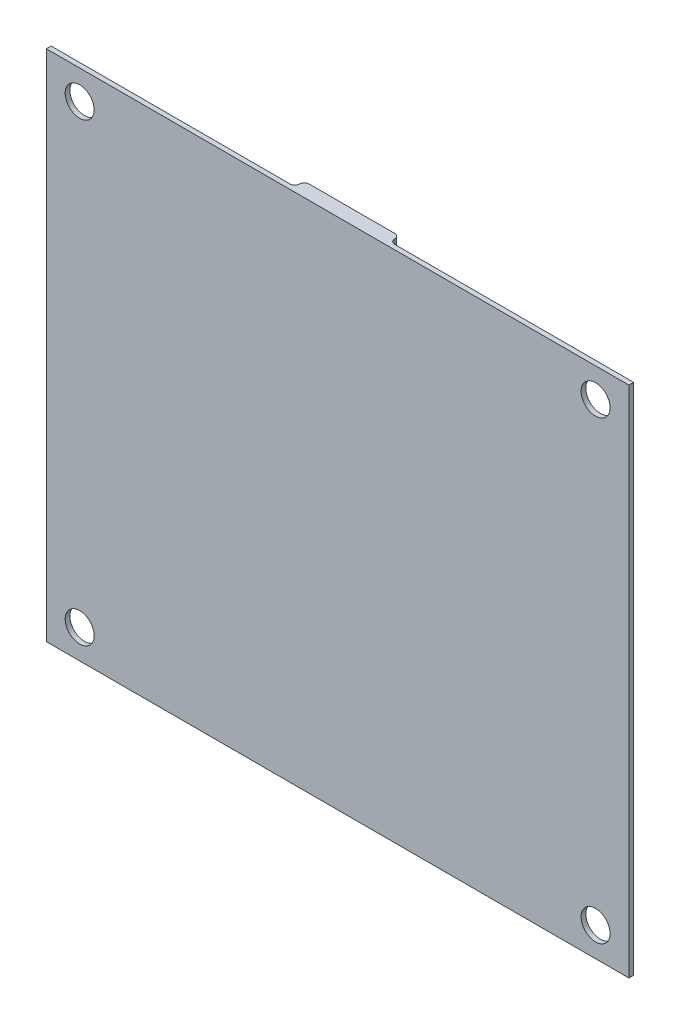
SolidWorks part; units mm, degrees
ref_plane "Alzado" through (0, 0, 0) normal (0, 0, 1) x (1, 0, 0)
ref_plane "Planta" through (0, 0, 0) normal (0, 1, 0) x (1, 0, 0)
ref_plane "Vista lateral" through (0, 0, 0) normal (1, 0, 0) x (0, 0, -1)
sketch "Croquis1" plane through (0, 0, 0) normal (0, 0, 1) x (1, 0, 0)
  line L8 (122.5, -282.5) -> (122.5, -65.5153)
  line L9 (-122.5, -281.5) -> (-18.1384, -281.5)
  line L10 (-122.5, -65.5153) -> (-122.5, -281.5)
  line L11 (122.5, -65.5153) -> (-122.5, -65.5153)
  line L12 (122.5, -281.5) -> (122.5, -65.5153)
  line L13 (-122.5, -281.5) -> (122.5, -281.5)
  line L14 (-122.5, -65.5153) -> (-122.5, -281.5)
  line L15 (122.5, -65.5153) -> (-122.5, -65.5153)
  circle A14 centre (-108.5046, -269.2661) radius 6.1
  circle A15 centre (-108.5046, -269.2661) radius 6.1
  circle A17 centre (108.5046, -269.2661) radius 6.1
  circle A18 centre (108.5046, -269.2661) radius 6.1
  circle A20 centre (108.5046, -77.7492) radius 6.1
  circle A21 centre (108.5046, -77.7492) radius 6.1
  circle A23 centre (-108.5046, -77.7492) radius 6.1
  circle A24 centre (-108.5046, -77.7492) radius 6.1
  dimension "D1" = 1
  dimension "D2" = 1
  dimension "D3" = 1
  dimension "D4" = 1
  dimension "D5" = 1
extrude "Saliente-Extruir1" add sketch "Croquis1" along normal blind 2
sketch "Croquis2" plane through (0, 0, 0) normal (0, 0, -1) x (-1, 0, 0)
  line L0 (0, -65.5153) -> (0, -281.5) construction
  line L1 (-20, -65.5153) -> (20, -65.5153)
  line L2 (-20, -65.5153) -> (-20, -95.5153)
  line L3 (-20, -95.5153) -> (20, -95.5153)
  line L4 (20, -65.5153) -> (20, -95.5153)
  line L5 (-122.5, -65.5153) -> (122.5, -65.5153) construction
  line L6 (122.5, -281.5) -> (-122.5, -281.5) construction
  dimension "D1" = 40
  dimension "D2" = 30
extrude "Saliente-Extruir2" add sketch "Croquis2" along normal blind 4
fillet "Redondeo1" radius 2 6 edges at (-20, -80.5153, -4) (0, -95.5153, 0) (0, -95.5153, -4) (20, -80.5153, -4)
